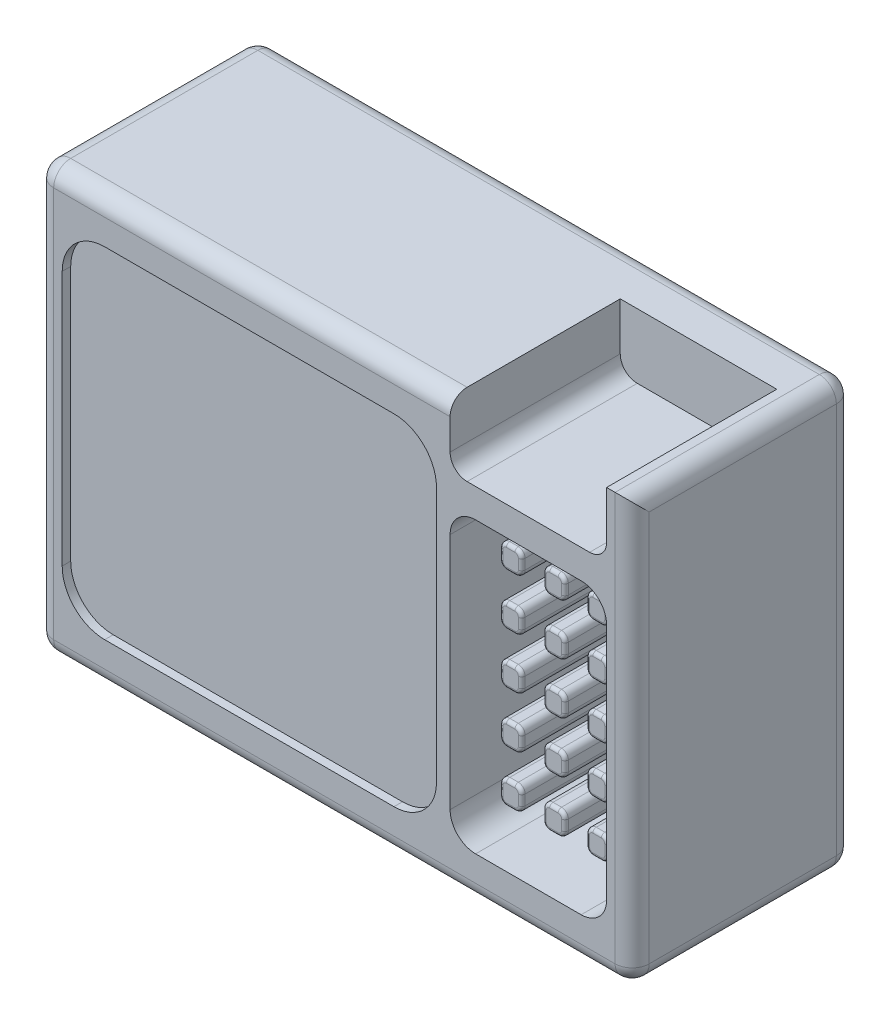
SolidWorks part; units mm, degrees
note: The reader was unsure of these and kept them because the rebuilt part matched: shared geometry of "Sketch2<4>", "Sketch2<5>".
ref_plane "Front Plane" through (0, 0, 0) normal (0, 0, 1) x (1, 0, 0)
ref_plane "Top Plane" through (0, 0, 0) normal (0, 1, 0) x (1, 0, 0)
ref_plane "Right Plane" through (0, 0, 0) normal (1, 0, 0) x (0, 0, -1)
sketch "Sketch1" plane through (0, 0, 0) normal (0, 0, 1) x (1, 0, 0)
  line L1 (-17.5, -12.5) -> (17.5, -12.5)
  line L2 (-17.5, -12.5) -> (-17.5, 12.5)
  line L3 (-17.5, 12.5) -> (17.5, 12.5)
  line L4 (17.5, -12.5) -> (17.5, 12.5)
  line L5 (-17.5, -12.5) -> (17.5, 12.5) construction
  line L6 (-17.5, 12.5) -> (17.5, -12.5) construction
  point P0 (0, 0)
  dimension "D1" = 25
  dimension "D2" = 35
extrude "Boss-Extrude1" add sketch "Sketch1" along normal blind 13
sketch "Sketch2" plane through (0, 0, 13) normal (0, 0, 1) x (1, 0, 0)
  line L0 (-17.5, 12.5) -> (-17.5, -12.5) construction
  line L1 (-13.5, 10) -> (3.5, 10)
  line L2 (-16, 7.5) -> (-16, -7.5)
  line L3 (-13.5, -10) -> (3.5, -10)
  line L4 (6, 7.5) -> (6, -7.5)
  line L5 (17.5, 12.5) -> (-17.5, 12.5) construction
  line L10 (6.8, 12.5) -> (16, 12.5)
  line L11 (6.8, 12.5) -> (6.8, 9.7)
  line L12 (7.8, 8.7) -> (15, 8.7)
  line L13 (16, 12.5) -> (16, 9.7)
  line L14 (10.75, 4.8) -> (10.75, 4.2)
  line L15 (8.61, 5.2) -> (9.11, 5.2)
  line L16 (6.8, 5.5) -> (6.8, -8.5)
  line L17 (8.21, 4.8) -> (8.21, 4.2)
  line L18 (14.5, 7) -> (8.3, 7)
  line L19 (16, 5.5) -> (16, -8.5)
  line L20 (14.5, -10) -> (8.3, -10)
  line L21 (8.61, 3.8) -> (9.11, 3.8)
  line L22 (9.51, 4.8) -> (9.51, 4.2)
  line L23 (11.15, 5.2) -> (11.65, 5.2)
  line L24 (12.05, 4.8) -> (12.05, 4.2)
  line L25 (11.15, 3.8) -> (11.65, 3.8)
  line L26 (13.29, 4.8) -> (13.29, 4.2)
  line L27 (13.69, 5.2) -> (14.19, 5.2)
  line L28 (14.59, 4.8) -> (14.59, 4.2)
  line L29 (13.69, 3.8) -> (14.19, 3.8)
  line L30 (10.75, 1.8) -> (10.75, 1.2)
  line L31 (11.15, 2.2) -> (11.65, 2.2)
  line L32 (12.05, 1.8) -> (12.05, 1.2)
  line L33 (11.15, 0.8) -> (11.65, 0.8)
  line L34 (13.29, 1.8) -> (13.29, 1.2)
  line L35 (13.69, 2.2) -> (14.19, 2.2)
  line L36 (14.59, 1.8) -> (14.59, 1.2)
  line L37 (13.69, 0.8) -> (14.19, 0.8)
  line L38 (10.75, -1.2) -> (10.75, -1.8)
  line L39 (11.15, -0.8) -> (11.65, -0.8)
  line L40 (12.05, -1.2) -> (12.05, -1.8)
  line L41 (11.15, -2.2) -> (11.65, -2.2)
  line L42 (13.29, -1.2) -> (13.29, -1.8)
  line L43 (13.69, -0.8) -> (14.19, -0.8)
  line L44 (14.59, -1.2) -> (14.59, -1.8)
  line L45 (13.69, -2.2) -> (14.19, -2.2)
  line L46 (10.75, -4.2) -> (10.75, -4.8)
  line L47 (11.15, -3.8) -> (11.65, -3.8)
  line L48 (12.05, -4.2) -> (12.05, -4.8)
  line L49 (11.15, -5.2) -> (11.65, -5.2)
  line L50 (13.29, -4.2) -> (13.29, -4.8)
  line L51 (13.69, -3.8) -> (14.19, -3.8)
  line L52 (14.59, -4.2) -> (14.59, -4.8)
  line L53 (13.69, -5.2) -> (14.19, -5.2)
  line L54 (10.75, -7.2) -> (10.75, -7.8)
  line L55 (11.15, -6.8) -> (11.65, -6.8)
  line L56 (12.05, -7.2) -> (12.05, -7.8)
  line L57 (11.15, -8.2) -> (11.65, -8.2)
  line L58 (13.29, -7.2) -> (13.29, -7.8)
  line L59 (13.69, -6.8) -> (14.19, -6.8)
  line L60 (14.59, -7.2) -> (14.59, -7.8)
  line L61 (13.69, -8.2) -> (14.19, -8.2)
  line L62 (8.21, 1.8) -> (8.21, 1.2)
  line L63 (8.61, 2.2) -> (9.11, 2.2)
  line L64 (9.51, 1.8) -> (9.51, 1.2)
  line L65 (8.61, 0.8) -> (9.11, 0.8)
  line L66 (8.21, -1.2) -> (8.21, -1.8)
  line L67 (8.61, -0.8) -> (9.11, -0.8)
  line L68 (9.51, -1.2) -> (9.51, -1.8)
  line L69 (8.61, -2.2) -> (9.11, -2.2)
  line L70 (8.21, -4.2) -> (8.21, -4.8)
  line L71 (8.61, -3.8) -> (9.11, -3.8)
  line L72 (9.51, -4.2) -> (9.51, -4.8)
  line L73 (8.61, -5.2) -> (9.11, -5.2)
  line L74 (8.21, -7.2) -> (8.21, -7.8)
  line L75 (8.61, -6.8) -> (9.11, -6.8)
  line L76 (9.51, -7.2) -> (9.51, -7.8)
  line L77 (8.61, -8.2) -> (9.11, -8.2)
  arc A0 (3.5, 10) -> (6, 7.5) centre (3.5, 7.5) cw
  arc A1 (-16, -7.5) -> (-13.5, -10) centre (-13.5, -7.5) ccw
  arc A2 (-13.5, 10) -> (-16, 7.5) centre (-13.5, 7.5) ccw
  arc A3 (3.5, -10) -> (6, -7.5) centre (3.5, -7.5) ccw
  arc A4 (14.5, 7) -> (16, 5.5) centre (14.5, 5.5) cw
  arc A5 (6.8, 5.5) -> (8.3, 7) centre (8.3, 5.5) cw
  arc A6 (16, -8.5) -> (14.5, -10) centre (14.5, -8.5) cw
  arc A7 (6.8, -8.5) -> (8.3, -10) centre (8.3, -8.5) ccw
  arc A8 (15, 8.7) -> (16, 9.7) centre (15, 9.7) ccw
  arc A9 (6.8, 9.7) -> (7.8, 8.7) centre (7.8, 9.7) ccw
  arc A10 (9.11, 3.8) -> (9.51, 4.2) centre (9.11, 4.2) ccw
  arc A11 (8.21, 4.2) -> (8.61, 3.8) centre (8.61, 4.2) ccw
  arc A12 (9.11, 5.2) -> (9.51, 4.8) centre (9.11, 4.8) cw
  arc A13 (8.61, 5.2) -> (8.21, 4.8) centre (8.61, 4.8) ccw
  arc A14 (11.15, 5.2) -> (10.75, 4.8) centre (11.15, 4.8) ccw
  arc A15 (10.75, 4.2) -> (11.15, 3.8) centre (11.15, 4.2) ccw
  arc A16 (11.65, 5.2) -> (12.05, 4.8) centre (11.65, 4.8) cw
  arc A17 (11.65, 3.8) -> (12.05, 4.2) centre (11.65, 4.2) ccw
  arc A18 (13.69, 5.2) -> (13.29, 4.8) centre (13.69, 4.8) ccw
  arc A19 (13.29, 4.2) -> (13.69, 3.8) centre (13.69, 4.2) ccw
  arc A20 (14.19, 5.2) -> (14.59, 4.8) centre (14.19, 4.8) cw
  arc A21 (14.19, 3.8) -> (14.59, 4.2) centre (14.19, 4.2) ccw
  arc A22 (11.15, 2.2) -> (10.75, 1.8) centre (11.15, 1.8) ccw
  arc A23 (10.75, 1.2) -> (11.15, 0.8) centre (11.15, 1.2) ccw
  arc A24 (11.65, 2.2) -> (12.05, 1.8) centre (11.65, 1.8) cw
  arc A25 (11.65, 0.8) -> (12.05, 1.2) centre (11.65, 1.2) ccw
  arc A26 (13.69, 2.2) -> (13.29, 1.8) centre (13.69, 1.8) ccw
  arc A27 (13.29, 1.2) -> (13.69, 0.8) centre (13.69, 1.2) ccw
  arc A28 (14.19, 2.2) -> (14.59, 1.8) centre (14.19, 1.8) cw
  arc A29 (14.19, 0.8) -> (14.59, 1.2) centre (14.19, 1.2) ccw
  arc A30 (11.15, -0.8) -> (10.75, -1.2) centre (11.15, -1.2) ccw
  arc A31 (10.75, -1.8) -> (11.15, -2.2) centre (11.15, -1.8) ccw
  arc A32 (11.65, -0.8) -> (12.05, -1.2) centre (11.65, -1.2) cw
  arc A33 (11.65, -2.2) -> (12.05, -1.8) centre (11.65, -1.8) ccw
  arc A34 (13.69, -0.8) -> (13.29, -1.2) centre (13.69, -1.2) ccw
  arc A35 (13.29, -1.8) -> (13.69, -2.2) centre (13.69, -1.8) ccw
  arc A36 (14.19, -0.8) -> (14.59, -1.2) centre (14.19, -1.2) cw
  arc A37 (14.19, -2.2) -> (14.59, -1.8) centre (14.19, -1.8) ccw
  arc A38 (11.15, -3.8) -> (10.75, -4.2) centre (11.15, -4.2) ccw
  arc A39 (10.75, -4.8) -> (11.15, -5.2) centre (11.15, -4.8) ccw
  arc A40 (11.65, -3.8) -> (12.05, -4.2) centre (11.65, -4.2) cw
  arc A41 (11.65, -5.2) -> (12.05, -4.8) centre (11.65, -4.8) ccw
  arc A42 (13.69, -3.8) -> (13.29, -4.2) centre (13.69, -4.2) ccw
  arc A43 (13.29, -4.8) -> (13.69, -5.2) centre (13.69, -4.8) ccw
  arc A44 (14.19, -3.8) -> (14.59, -4.2) centre (14.19, -4.2) cw
  arc A45 (14.19, -5.2) -> (14.59, -4.8) centre (14.19, -4.8) ccw
  arc A46 (11.15, -6.8) -> (10.75, -7.2) centre (11.15, -7.2) ccw
  arc A47 (10.75, -7.8) -> (11.15, -8.2) centre (11.15, -7.8) ccw
  arc A48 (11.65, -6.8) -> (12.05, -7.2) centre (11.65, -7.2) cw
  arc A49 (11.65, -8.2) -> (12.05, -7.8) centre (11.65, -7.8) ccw
  arc A50 (13.69, -6.8) -> (13.29, -7.2) centre (13.69, -7.2) ccw
  arc A51 (13.29, -7.8) -> (13.69, -8.2) centre (13.69, -7.8) ccw
  arc A52 (14.19, -6.8) -> (14.59, -7.2) centre (14.19, -7.2) cw
  arc A53 (14.19, -8.2) -> (14.59, -7.8) centre (14.19, -7.8) ccw
  arc A54 (8.61, 2.2) -> (8.21, 1.8) centre (8.61, 1.8) ccw
  arc A55 (8.21, 1.2) -> (8.61, 0.8) centre (8.61, 1.2) ccw
  arc A56 (9.11, 2.2) -> (9.51, 1.8) centre (9.11, 1.8) cw
  arc A57 (9.11, 0.8) -> (9.51, 1.2) centre (9.11, 1.2) ccw
  arc A58 (8.61, -0.8) -> (8.21, -1.2) centre (8.61, -1.2) ccw
  arc A59 (8.21, -1.8) -> (8.61, -2.2) centre (8.61, -1.8) ccw
  arc A60 (9.11, -0.8) -> (9.51, -1.2) centre (9.11, -1.2) cw
  arc A61 (9.11, -2.2) -> (9.51, -1.8) centre (9.11, -1.8) ccw
  arc A62 (8.61, -3.8) -> (8.21, -4.2) centre (8.61, -4.2) ccw
  arc A63 (8.21, -4.8) -> (8.61, -5.2) centre (8.61, -4.8) ccw
  arc A64 (9.11, -3.8) -> (9.51, -4.2) centre (9.11, -4.2) cw
  arc A65 (9.11, -5.2) -> (9.51, -4.8) centre (9.11, -4.8) ccw
  arc A66 (8.61, -6.8) -> (8.21, -7.2) centre (8.61, -7.2) ccw
  arc A67 (8.21, -7.8) -> (8.61, -8.2) centre (8.61, -7.8) ccw
  arc A68 (9.11, -6.8) -> (9.51, -7.2) centre (9.11, -7.2) cw
  arc A69 (9.11, -8.2) -> (9.51, -7.8) centre (9.11, -7.8) ccw
  point P4 (-16, 0)
  point P10 (6, 10)
  point P15 (-16, 10)
  point P28 (6, -10)
  point P31 (16, 7)
  point P34 (6.8, 7)
  point P39 (6.8, -10)
  point P44 (6.8, 8.7)
  point P51 (9.51, 3.8)
  point P54 (8.21, 3.8)
  point P57 (9.51, 5.2)
  point P60 (11.4, 5.2)
  point P61 (11.4, 7)
  point P62 (14.59, -1.5)
  point P231 (16, -1.5)
  dimension "D4" = 2.5
  dimension "D9" = 2.5
  dimension "D10" = 1.5
  dimension "D11" = 1
  dimension "D14" = 0.4
  dimension "D1" = 22
  dimension "D2" = 20
  dimension "D3" = 1.5
  dimension "D5" = 9.2
  dimension "D6" = 3.8
  dimension "D7" = 17
  dimension "D8" = 0.8
  dimension "D12" = 1.4
  dimension "D13" = 1.3
  dimension "D15" = 3
  dimension "D16" = 5
extrude "Cut-Extrude1" cut sketch "Sketch2" against normal blind 0.5 contours A3 L3 A1 L2 A2 L1 A0 L4
extrude "Cut-Extrude2" cut sketch "Sketch2<4>" against normal blind 10 contours L16 A7 L20 A6 L19 A4 L18 A5 | A9 L12 A8 L13 L10 L11
sketch "Sketch2<4>" plane through (0, 0, 13) normal (0, 0, 1) x (1, 0, 0) same geometry as "Sketch2"
extrude "Cut-Extrude3" cut sketch "Sketch2<5>" against normal blind 1.5 contours L77 A69 L76 A68 L75 A66 L74 A67 | L73 A65 L72 A64 L71 A62 L70 A63 | L57 A49 L56 A48 L55 A46 L54 A47 | L49 A41 L48 A40 L47 A38 L46 A39 | L53 A45 L52 A44 L51 A42 L50 A43 | L61 A53 L60 A52 L59 A50 L58 A51 | L45 A37 L44 A36 L43 A34 L42 A35 | L41 A33 L40 A32 L39 A30 L38 A31 | L69 A61 L68 A60 L67 A58 L66 A59 | L65 A57 L64 A56 L63 A54 L62 A55 | L33 A25 L32 A24 L31 A22 L30 A23 | L37 A29 L36 A28 L35 A26 L34 A27 | L25 A17 L24 A16 L23 A14 L14 A15 | L29 A21 L28 A20 L27 A18 L26 A19 | L15 A13 L17 A11 L21 A10 L22 A12
sketch "Sketch2<5>" plane through (0, 0, 13) normal (0, 0, 1) x (1, 0, 0) same geometry as "Sketch2"
fillet "Fillet1" radius 1 12 edges at (17.5, -12.5, 6.5) (17.5, 0, 13) (17.5, 12.5, 6.5) (17.5, 0, 0) (-17.5, 12.5, 6.5) (-17.5, 0, 13) (-17.5, -12.5, 6.5) (-17.5, 0, 0) (0, -12.5, 0) (-5.35, 12.5, 13) (0, 12.5, 0) (0, -12.5, 13)
fillet "Fillet3" radius 0.2 120 edges at (11.4, 3.8, 11.5) (10.8672, 3.9172, 11.5) (10.75, 4.5, 11.5) (10.8672, 5.0828, 11.5) (11.9328, 3.9172, 11.5) (11.4, 5.2, 11.5) (11.9328, 5.0828, 11.5) (12.05, 4.5, 11.5) (13.94, 0.8, 11.5) (13.4072, 0.9172, 11.5) (13.29, 1.5, 11.5) (13.4072, 2.0828, 11.5) (14.4728, 0.9172, 11.5) (13.94, 2.2, 11.5) (14.4728, 2.0828, 11.5) (14.59, 1.5, 11.5) (11.4, 0.8, 11.5) (10.8672, 0.9172, 11.5) (10.75, 1.5, 11.5) (10.8672, 2.0828, 11.5) (11.9328, 0.9172, 11.5) (11.4, 2.2, 11.5) (11.9328, 2.0828, 11.5) (12.05, 1.5, 11.5) (8.86, 0.8, 11.5) (8.3272, 0.9172, 11.5) (8.21, 1.5, 11.5) (8.3272, 2.0828, 11.5) (9.3928, 0.9172, 11.5) (8.86, 2.2, 11.5) (9.3928, 2.0828, 11.5) (9.51, 1.5, 11.5) (13.94, 3.8, 11.5) (13.4072, 3.9172, 11.5) (13.29, 4.5, 11.5) (13.4072, 5.0828, 11.5) (14.4728, 3.9172, 11.5) (13.94, 5.2, 11.5) (14.4728, 5.0828, 11.5) (14.59, 4.5, 11.5) (9.3928, 3.9172, 11.5) (8.86, 3.8, 11.5) (8.3272, 3.9172, 11.5) (8.21, 4.5, 11.5) (8.3272, 5.0828, 11.5) (8.86, 5.2, 11.5) (9.3928, 5.0828, 11.5) (9.51, 4.5, 11.5) (13.94, -5.2, 11.5) (13.4072, -5.0828, 11.5) (13.29, -4.5, 11.5) (13.4072, -3.9172, 11.5) (14.4728, -5.0828, 11.5) (13.94, -3.8, 11.5) (14.4728, -3.9172, 11.5) (14.59, -4.5, 11.5) (11.4, -5.2, 11.5) (10.8672, -5.0828, 11.5) (10.75, -4.5, 11.5) (10.8672, -3.9172, 11.5) (11.9328, -5.0828, 11.5) (11.4, -3.8, 11.5) (11.9328, -3.9172, 11.5) (12.05, -4.5, 11.5) (11.4, -8.2, 11.5) (10.8672, -8.0828, 11.5) (10.75, -7.5, 11.5) (10.8672, -6.9172, 11.5) (11.9328, -8.0828, 11.5) (11.4, -6.8, 11.5) (11.9328, -6.9172, 11.5) (12.05, -7.5, 11.5) (8.86, -5.2, 11.5) (8.3272, -5.0828, 11.5) (8.21, -4.5, 11.5) (8.3272, -3.9172, 11.5) (9.3928, -5.0828, 11.5) (8.86, -3.8, 11.5) (9.3928, -3.9172, 11.5) (9.51, -4.5, 11.5) (13.94, -8.2, 11.5) (13.4072, -8.0828, 11.5) (13.29, -7.5, 11.5) (13.4072, -6.9172, 11.5) (14.4728, -8.0828, 11.5) (13.94, -6.8, 11.5) (14.4728, -6.9172, 11.5) (14.59, -7.5, 11.5) (13.94, -2.2, 11.5) (13.4072, -2.0828, 11.5) (13.29, -1.5, 11.5) (13.4072, -0.9172, 11.5) (14.4728, -2.0828, 11.5) (13.94, -0.8, 11.5) (14.4728, -0.9172, 11.5) (14.59, -1.5, 11.5) (11.4, -2.2, 11.5) (10.8672, -2.0828, 11.5) (10.75, -1.5, 11.5) (10.8672, -0.9172, 11.5) (11.9328, -2.0828, 11.5) (11.4, -0.8, 11.5) (11.9328, -0.9172, 11.5) (12.05, -1.5, 11.5) (8.86, -2.2, 11.5) (8.3272, -2.0828, 11.5) (8.21, -1.5, 11.5) (8.3272, -0.9172, 11.5) (9.3928, -2.0828, 11.5) (8.86, -0.8, 11.5) (9.3928, -0.9172, 11.5) (9.51, -1.5, 11.5) (8.86, -8.2, 11.5) (8.3272, -8.0828, 11.5) (8.21, -7.5, 11.5) (8.3272, -6.9172, 11.5) (9.3928, -8.0828, 11.5) (8.86, -6.8, 11.5) (9.3928, -6.9172, 11.5) (9.51, -7.5, 11.5)
